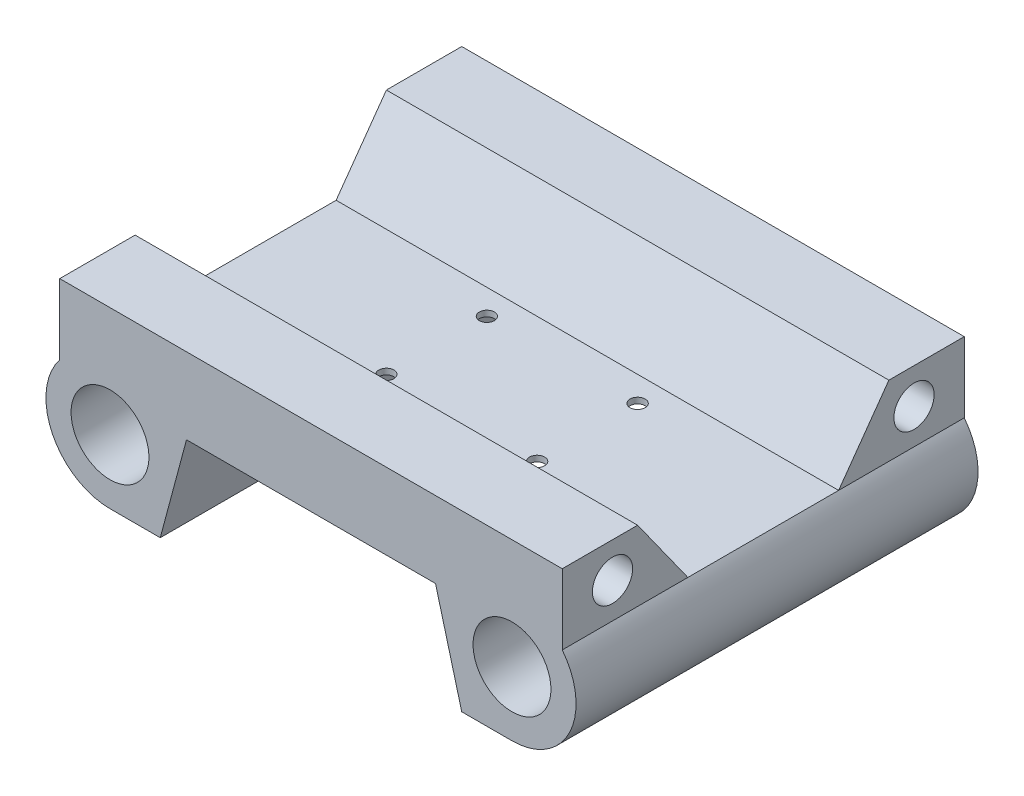
SolidWorks part; units mm, degrees
material "ABS"
ref_plane "Plano frontal" through (0, 0, 0) normal (0, 0, 1) x (1, 0, 0)
ref_plane "Plano superior" through (0, 0, 0) normal (0, 1, 0) x (1, 0, 0)
ref_plane "Plano direito" through (0, 0, 0) normal (1, 0, 0) x (0, 0, -1)
sketch "Esboço1" plane through (0, 0, 0) normal (0, 0, 1) x (1, 0, 0)
  line L0 (-63.5982, -1.8406) -> (63.0213, -1.8406) construction
  line L1 (-63.5982, 6.1594) -> (-63.5982, -1.8406) construction
  line L2 (-40, -25.499) -> (-30, -25.499)
  line L3 (-30, -25.499) -> (-24.7752, -6)
  line L4 (-50, -4.8406) -> (-50, 9.1594)
  line L5 (-50, 9.1594) -> (50, 9.1594)
  line L6 (0, 0) -> (0, -46.1263) construction
  line L7 (50, 9.1594) -> (50, -4.8406)
  line L8 (30, -25.499) -> (24.7752, -6)
  line L9 (40, -25.499) -> (30, -25.499)
  line L11 (-24.7752, -6) -> (24.7752, -6)
  line L12 (-40, -12.7495) -> (40, -12.7495) construction
  line L13 (-63.5982, 6.1594) -> (63.0213, 6.1594) construction
  circle A0 centre (-40, -12.7495) radius 7.75
  circle A1 centre (40, -12.7495) radius 7.75
  arc A2 (40, -25.499) -> (50, -4.8406) centre (40, -12.7495) ccw
  arc A3 (-50, -4.8406) -> (-40, -25.499) centre (-40, -12.7495) ccw
  point P14 (-63.5982, 2.1594)
  point P15 (-50, 2.1594)
  point P17 (0, -12.2866)
  point P24 (40, 0)
  point P27 (-40, 0)
  dimension "D1" = 15.5
  dimension "D7" = 14
  dimension "D10" = 12.7495
  dimension "D2" = 100
  dimension "D3" = 75
  dimension "D4" = 10
  dimension "D5" = 6.7495
  dimension "D6" = 40
  dimension "D8" = 6
  dimension "D11" = 8
extrude "Ressalto-extrusão1" add sketch "Esboço1" along normal blind 80
sketch "Esboço2" plane through (0, -25.499, 0) normal (0, -1, 0) x (1, 0, 0)
  line L0 (15, 50) -> (15, 30) construction
  line L1 (-52.7495, 40) -> (52.7495, 40) construction
  line L2 (-52.7495, 80) -> (-52.7495, 0) construction
  line L3 (52.7495, 0) -> (52.7495, 80) construction
  line L6 (0, 0) -> (0, 80) construction
  line L7 (-24.7752, 80) -> (24.7752, 80) construction
  line L8 (-15, 50) -> (-15, 30) construction
  line L9 (-24.7752, 0) -> (24.7752, 0) construction
  line L10 (-7.5, 15) -> (7.5, 15)
  line L11 (-7.5, 15) -> (-7.5, 0)
  line L12 (-7.5, 0) -> (7.5, 0)
  line L13 (7.5, 15) -> (7.5, 0)
  line L14 (-7.5, 15) -> (7.5, 0) construction
  line L15 (-7.5, 0) -> (7.5, 15) construction
  circle A0 centre (15, 50) radius 1.5
  circle A1 centre (15, 30) radius 1.5
  circle A2 centre (-15, 30) radius 1.5
  circle A3 centre (-15, 50) radius 1.5
  point P10 (15, 40)
  point P20 (0, 7.5)
  dimension "D1" = 20
  dimension "D2" = 3
  dimension "D3" = 15
  dimension "D4" = 15
  dimension "D5" = 15
extrude "Corte-extrusão1" cut sketch "Esboço2" against normal blind 30
sketch "Esboço4" plane through (-50, 0, 0) normal (-1, 0, 0) x (0, 0, 1)
  line L0 (10, 2.1594) -> (70, 2.1594) construction
  line L1 (80, -4.8406) -> (0, -4.8406) construction
  line L3 (80, 9.1594) -> (0, 9.1594) construction
  line L4 (15, 9.1594) -> (25, -4.8406)
  line L5 (25, -4.8406) -> (55, -4.8406)
  line L7 (55, -4.8406) -> (65, 9.1594)
  line L8 (65, 9.1594) -> (15, 9.1594)
  line L9 (0, 9.1594) -> (0, -4.8406) construction
  circle A0 centre (10, 2.1594) radius 4
  circle A1 centre (70, 2.1594) radius 4
  point P6 (40, 2.1594)
  point P9 (40, 9.1594)
  point P12 (40, -4.8406)
  point P14 (55, -4.8406)
  point P17 (40, 9.1594)
  point P18 (16.395, 8.0005)
  point P19 (23.3148, -4.9995)
  point P22 (0, 2.1594)
  point P23 (25.0059, -4.8406)
  dimension "D2" = 8
  dimension "D1" = 60
  dimension "D4" = 30
  dimension "D5" = 50
extrude "Corte-extrusão3" cut sketch "Esboço4" against normal through all both and the other way through all
